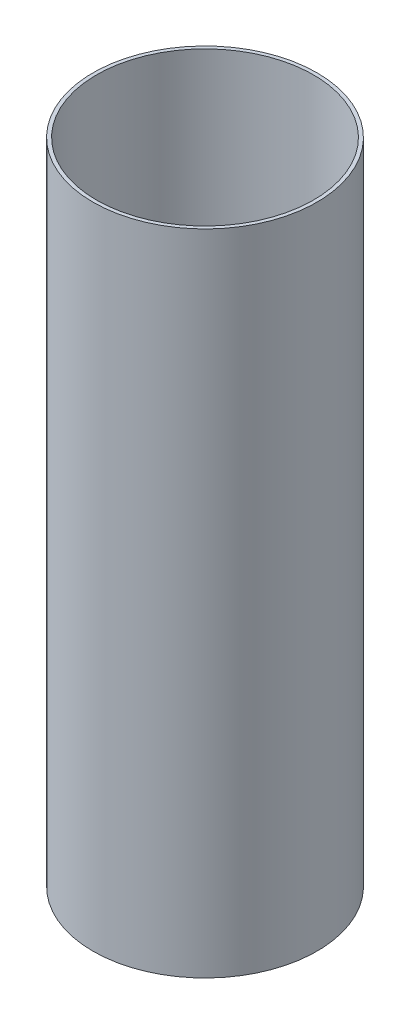
SolidWorks part; units mm, degrees
ref_plane "Front Plane" through (0, 0, 0) normal (0, 0, 1) x (1, 0, 0)
ref_plane "Top Plane" through (0, 0, 0) normal (0, 1, 0) x (1, 0, 0)
ref_plane "Right Plane" through (0, 0, 0) normal (1, 0, 0) x (0, 0, -1)
sketch "Sketch1" plane through (0, 0, 0) normal (0, 1, 0) x (1, 0, 0)
  circle A0 centre (0, 0) radius 18.4
  circle A1 centre (0, 0) radius 19
  dimension "D1" = 38
  dimension "D2" = 0.6
extrude "Boss-Extrude1" add sketch "Sketch1" along normal mid plane 110
